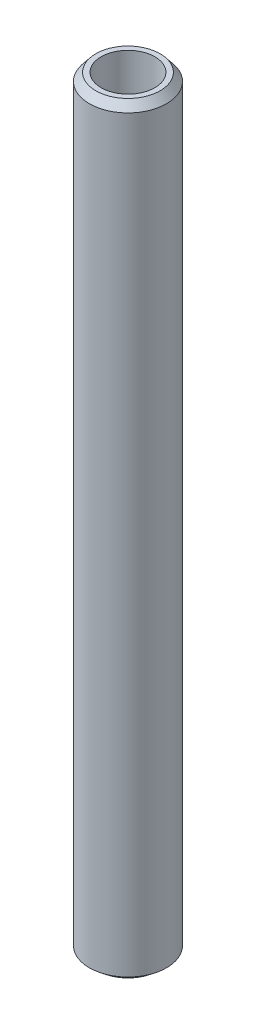
SolidWorks part; units mm, degrees
ref_plane "Front Plane" through (0, 0, 0) normal (0, 0, 1) x (1, 0, 0)
ref_plane "Top Plane" through (0, 0, 0) normal (0, 1, 0) x (1, 0, 0)
ref_plane "Right Plane" through (0, 0, 0) normal (1, 0, 0) x (0, 0, -1)
sketch "Sketch1" plane through (0, 0, 0) normal (0, 1, 0) x (1, 0, 0)
  circle A0 centre (0, 0) radius 22.5
  dimension "SHAFT_OD" = 45
extrude "Boss-Extrude1" add sketch "Sketch1" along normal blind 444.6797
sketch "Sketch2" plane through (0, 0, 0) normal (0, 1, 0) x (1, 0, 0)
  circle A0 centre (0, 0) radius 15.6587
  dimension "BORE_D" = 31.3175
extrude "Cut-Extrude1" cut sketch "Sketch2" along normal through all
chamfer "Chamfer1" distance 4.6477 angle 39.006 2 edges at (0, 444.6797, 22.5) (0, 0, 22.5) first distance on face at (0, 444.6797, 22.5) first distance on face at (0, 0, 15.6587)
